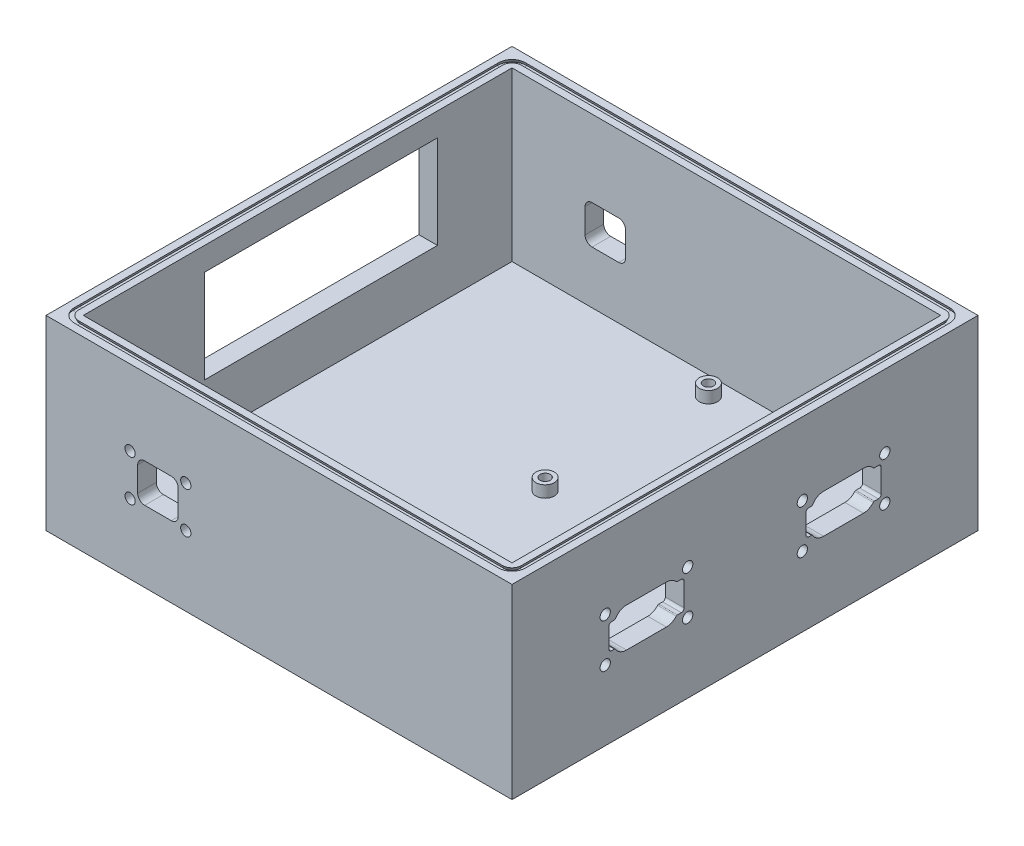
SolidWorks part; units mm, degrees
ref_plane "Front Plane" through (0, 0, 0) normal (0, 0, 1) x (1, 0, 0)
ref_plane "Top Plane" through (0, 0, 0) normal (0, 1, 0) x (1, 0, 0)
ref_plane "Right Plane" through (0, 0, 0) normal (1, 0, 0) x (0, 0, -1)
sketch "Sketch1" plane through (0, 0, 0) normal (0, 1, 0) x (1, 0, 0)
  line L1 (0, 0) -> (254, 0)
  line L2 (0, 0) -> (0, 254)
  line L3 (0, 254) -> (254, 254)
  line L4 (254, 0) -> (254, 254)
  dimension "D1" = 254
  dimension "D2" = 254
extrude "Boss-Extrude1" add sketch "Sketch1" along normal blind 101.6
sketch "12 pin hole" [suppressed] plane through (254, 0, 0) normal (1, 0, 0) x (0, 0, -1)
  line L8 (50.8, 10.16) -> (95.758, 10.16) construction
  line L9 (50.8, 10.16) -> (50.8, 34.036) construction
  line L10 (50.8, 34.036) -> (95.758, 34.036) construction
  line L11 (95.758, 10.16) -> (95.758, 34.036) construction
  line L12 (55.7357, 28.956) -> (54.2925, 28.956)
  line L13 (52.7685, 27.432) -> (52.7685, 16.764)
  line L14 (54.2925, 15.24) -> (55.7357, 15.24)
  line L16 (90.087, 29.972) -> (92.2655, 29.972)
  line L17 (93.7895, 28.448) -> (93.7895, 15.748)
  line L18 (92.2655, 14.224) -> (90.087, 14.224)
  line L21 (62.4205, 25.654) -> (84.1375, 25.654) construction
  line L22 (62.4205, 25.654) -> (62.4205, 18.542) construction
  line L23 (62.4205, 18.542) -> (84.1375, 18.542) construction
  line L24 (84.1375, 25.654) -> (84.1375, 18.542) construction
  line L25 (62.4205, 32.7152) -> (84.1375, 32.7152)
  line L26 (62.4205, 11.4808) -> (84.1375, 11.4808)
  line L27 (52.7685, 22.098) -> (50.8, 22.098) construction
  line L28 (93.7895, 22.098) -> (95.758, 22.098) construction
  arc A4 (62.4205, 32.7152) -> (56.3868, 29.3222) centre (62.4205, 25.654) ccw
  arc A5 (89.5075, 30.2392) -> (84.1375, 32.7152) centre (84.1375, 25.654) ccw
  arc A6 (62.4205, 11.4808) -> (56.3868, 14.8738) centre (62.4205, 18.542) cw
  arc A7 (89.5075, 13.9568) -> (84.1375, 11.4808) centre (84.1375, 18.542) cw
  arc A8 (90.087, 29.972) -> (89.5075, 30.2392) centre (90.087, 30.734) cw
  arc A9 (90.087, 14.224) -> (89.5075, 13.9568) centre (90.087, 13.462) ccw
  arc A10 (55.7357, 15.24) -> (56.3868, 14.8738) centre (55.7357, 14.478) cw
  arc A11 (55.7357, 28.956) -> (56.3868, 29.3222) centre (55.7357, 29.718) ccw
  arc A12 (92.2655, 29.972) -> (93.7895, 28.448) centre (92.2655, 28.448) cw
  arc A13 (93.7895, 15.748) -> (92.2655, 14.224) centre (92.2655, 15.748) cw
  arc A14 (52.7685, 16.764) -> (54.2925, 15.24) centre (54.2925, 16.764) ccw
  arc A15 (54.2925, 28.956) -> (52.7685, 27.432) centre (54.2925, 27.432) ccw
  point P25 (50.8, 22.098)
  point P28 (52.7685, 22.098)
  point P29 (93.7895, 22.098)
  point P34 (62.4205, 22.098)
  point P35 (84.1375, 22.098)
  point P44 (73.279, 10.16)
  point P46 (73.279, 11.4808)
  point P59 (93.7895, 29.972)
  point P62 (93.7895, 14.224)
  point P65 (52.7685, 15.24)
  point P68 (52.7685, 28.956)
  dimension "D4" = 41.021
  dimension "D5" = 15.748
  dimension "D11" = 7.0612
  dimension "D12" = 0.762
  dimension "D13" = 1.524
  dimension "D1" = 44.958
  dimension "D2" = 23.876
  dimension "D8" = 13.716
  dimension "D9" = 21.2344
  dimension "D10" = 21.717
sketch "Sketch2" plane through (0, 101.6, 0) normal (0, 1, 0) x (1, 0, 0)
  line L0 (0, 254) -> (0, 0) construction
  line L1 (10.16, 10.16) -> (243.84, 10.16)
  line L2 (10.16, 10.16) -> (10.16, 243.84)
  line L3 (10.16, 243.84) -> (243.84, 243.84)
  line L4 (243.84, 10.16) -> (243.84, 243.84)
  line L5 (254, 254) -> (0, 254) construction
  line L6 (254, 0) -> (254, 254) construction
  line L7 (0, 0) -> (254, 0) construction
  dimension "D1" = 10.16
  dimension "D2" = 10.16
  dimension "D3" = 10.16
  dimension "D4" = 10.16
extrude "Cut-Extrude1" cut sketch "Sketch2" against normal blind 91.44
ref_plane "Plane1" through (0, 101.6, 0) normal (0, 1, 0) x (1, 0, 0)
sketch "Sketch3" plane through (0, 101.6, 0) normal (0, 1, 0) x (1, 0, 0)
  line L4 (6.35, 11.43) -> (6.35, 242.57)
  line L5 (243.84, 243.84) -> (10.16, 243.84) construction
  line L6 (10.16, 243.84) -> (10.16, 10.16) construction
  line L7 (243.84, 10.16) -> (243.84, 243.84) construction
  line L8 (10.16, 10.16) -> (243.84, 10.16) construction
  line L13 (11.43, 247.65) -> (242.57, 247.65)
  line L14 (247.65, 242.57) -> (247.65, 11.43)
  line L15 (242.57, 6.35) -> (11.43, 6.35)
  arc A0 (6.35, 242.57) -> (11.43, 247.65) centre (11.43, 242.57) cw
  arc A1 (242.57, 247.65) -> (247.65, 242.57) centre (242.57, 242.57) cw
  arc A2 (247.65, 11.43) -> (242.57, 6.35) centre (242.57, 11.43) cw
  arc A3 (11.43, 6.35) -> (6.35, 11.43) centre (11.43, 11.43) cw
  dimension "D5" = 5.08
  dimension "D1" = 3.81
  dimension "D2" = 3.81
  dimension "D3" = 3.81
  dimension "D4" = 3.81
ref_plane "Plane2" through (0, 0, 0) normal (0, 0, 1) x (1, 0, 0)
ref_plane "Plane3" through (0, 0, -15.24) normal (0, 0, 1) x (1, 0, 0)
sketch "Sketch4" plane through (0, 0, -15.24) normal (0, 0, 1) x (1, 0, 0)
  line L0 (4.064, 101.6) -> (3.2724, 99.822)
  line L1 (6.35, 101.6) -> (7.1416, 99.822)
  line L2 (3.2724, 99.822) -> (7.1416, 99.822)
  line L5 (4.064, 101.6) -> (6.35, 101.6)
  dimension "D1" = 1.778
  dimension "D2" = 2.286
  dimension "D3" = 66
  dimension "D4" = 66
sweep "Cut-Sweep2" cut profiles "Sketch4" path "Sketch3"
sketch "Sketch13" plane through (254, 0, 0) normal (1, 0, 0) x (0, 0, -1)
  line L0 (50.8, 38.1) -> (50.8, 0) construction
  line L1 (0, 0) -> (254, 0) construction
  line L2 (50.8, 38.1) -> (0, 38.1) construction
  line L3 (0, 101.6) -> (0, 0) construction
  line L4 (203.2, 0) -> (203.2, 38.1) construction
  line L5 (203.2, 38.1) -> (254, 38.1) construction
  line L6 (254, 101.6) -> (254, 0) construction
  line B0 (50.8, 38.1) -> (95.758, 38.1) construction
  line B1 (50.8, 38.1) -> (50.8, 61.976) construction
  line B2 (50.8, 61.976) -> (95.758, 61.976) construction
  line B3 (95.758, 38.1) -> (95.758, 61.976) construction
  line B4 (55.7357, 56.896) -> (54.2925, 56.896)
  line B5 (52.7685, 55.372) -> (52.7685, 44.704)
  line B6 (54.2925, 43.18) -> (55.7357, 43.18)
  line B7 (90.087, 57.912) -> (92.2655, 57.912)
  line B8 (93.7895, 56.388) -> (93.7895, 43.688)
  line B9 (92.2655, 42.164) -> (90.087, 42.164)
  line B10 (62.4205, 60.6552) -> (84.1375, 60.6552)
  line B11 (62.4205, 39.4208) -> (84.1375, 39.4208)
  arc B12 (62.4205, 60.6552) -> (56.3868, 57.2622) centre (62.4205, 53.594) ccw
  arc B13 (89.5075, 58.1792) -> (84.1375, 60.6552) centre (84.1375, 53.594) ccw
  arc B14 (62.4205, 39.4208) -> (56.3868, 42.8138) centre (62.4205, 46.482) cw
  arc B15 (89.5075, 41.8968) -> (84.1375, 39.4208) centre (84.1375, 46.482) cw
  arc B16 (90.087, 57.912) -> (89.5075, 58.1792) centre (90.087, 58.674) cw
  arc B17 (90.087, 42.164) -> (89.5075, 41.8968) centre (90.087, 41.402) ccw
  arc B18 (55.7357, 43.18) -> (56.3868, 42.8138) centre (55.7357, 42.418) cw
  arc B19 (55.7357, 56.896) -> (56.3868, 57.2622) centre (55.7357, 57.658) ccw
  arc B20 (92.2655, 57.912) -> (93.7895, 56.388) centre (92.2655, 56.388) cw
  arc B21 (93.7895, 43.688) -> (92.2655, 42.164) centre (92.2655, 43.688) cw
  arc B22 (52.7685, 44.704) -> (54.2925, 43.18) centre (54.2925, 44.704) ccw
  arc B23 (54.2925, 56.896) -> (52.7685, 55.372) centre (54.2925, 55.372) ccw
  line B24 (158.242, 38.1) -> (203.2, 38.1) construction
  line B25 (158.242, 38.1) -> (158.242, 61.976) construction
  line B26 (158.242, 61.976) -> (203.2, 61.976) construction
  line B27 (203.2, 38.1) -> (203.2, 61.976) construction
  line B28 (163.1777, 56.896) -> (161.7345, 56.896)
  line B29 (160.2105, 55.372) -> (160.2105, 44.704)
  line B30 (161.7345, 43.18) -> (163.1777, 43.18)
  line B31 (197.529, 57.912) -> (199.7075, 57.912)
  line B32 (201.2315, 56.388) -> (201.2315, 43.688)
  line B33 (199.7075, 42.164) -> (197.529, 42.164)
  line B34 (169.8625, 60.6552) -> (191.5795, 60.6552)
  line B35 (169.8625, 39.4208) -> (191.5795, 39.4208)
  arc B36 (169.8625, 60.6552) -> (163.8288, 57.2622) centre (169.8625, 53.594) ccw
  arc B37 (196.9495, 58.1792) -> (191.5795, 60.6552) centre (191.5795, 53.594) ccw
  arc B38 (169.8625, 39.4208) -> (163.8288, 42.8138) centre (169.8625, 46.482) cw
  arc B39 (196.9495, 41.8968) -> (191.5795, 39.4208) centre (191.5795, 46.482) cw
  arc B40 (197.529, 57.912) -> (196.9495, 58.1792) centre (197.529, 58.674) cw
  arc B41 (197.529, 42.164) -> (196.9495, 41.8968) centre (197.529, 41.402) ccw
  arc B42 (163.1777, 43.18) -> (163.8288, 42.8138) centre (163.1777, 42.418) cw
  arc B43 (163.1777, 56.896) -> (163.8288, 57.2622) centre (163.1777, 57.658) ccw
  arc B44 (199.7075, 57.912) -> (201.2315, 56.388) centre (199.7075, 56.388) cw
  arc B45 (201.2315, 43.688) -> (199.7075, 42.164) centre (199.7075, 43.688) cw
  arc B46 (160.2105, 44.704) -> (161.7345, 43.18) centre (161.7345, 44.704) ccw
  arc B47 (161.7345, 56.896) -> (160.2105, 55.372) centre (161.7345, 55.372) ccw
  dimension "D1" = 50.8
  dimension "D2" = 38.1
sketch_block_instance "Block7-3"
sketch_block "Block7" parameters "D6"=7.0612, "D7"=0.762, "D8"=1.524, "D1"=44.958, "D2"=23.876, "D3"=41.021, "D4"=21.2344, "D5"=21.717
sketch_block_instance "Block7-4"
extrude "Cut-Extrude10" cut sketch "Sketch13" against normal up to next
sketch "12 pin mount" plane through (254, 0, 0) normal (1, 0, 0) x (0, 0, -1)
  circle A0 centre (95.758, 61.976) radius 2.8
  circle A1 centre (95.758, 38.1) radius 2.8
  circle A2 centre (50.8, 38.1) radius 2.8
  circle A3 centre (50.8, 61.976) radius 2.8
  circle A4 centre (158.242, 61.976) radius 2.8
  circle A5 centre (203.2, 61.976) radius 2.8
  circle A6 centre (203.2, 38.1) radius 2.8
  circle A7 centre (158.242, 38.1) radius 2.8
  dimension "D1" = 5.6
extrude "Cut-Extrude3" cut sketch "12 pin mount" against normal blind 5.5
sketch "4 pin connector" plane through (0, 0, 0) normal (0, 0, 1) x (1, 0, 0)
  line L0 (76.2, 0) -> (76.2, 38.1) construction
  line L1 (0, 0) -> (254, 0) construction
  line L2 (76.2, 38.1) -> (254, 38.1) construction
  line L3 (254, 101.6) -> (254, 0) construction
  line L5 (45.847, 60.5536) -> (76.2, 60.5536) construction
  line L6 (45.847, 60.5536) -> (45.847, 38.1) construction
  line L7 (45.847, 38.1) -> (76.2, 38.1) construction
  line L8 (76.2, 60.5536) -> (76.2, 38.1) construction
  line L9 (53.7845, 59.817) -> (68.2625, 59.817)
  line L10 (49.9745, 56.007) -> (49.9745, 42.6466)
  line L11 (53.7845, 38.8366) -> (68.2625, 38.8366)
  line L12 (72.0725, 56.007) -> (72.0725, 42.6466)
  line L13 (61.0235, 38.8366) -> (61.0235, 59.817) construction
  line L14 (49.9745, 49.3268) -> (72.0725, 49.3268) construction
  arc A0 (68.2625, 59.817) -> (72.0725, 56.007) centre (68.2625, 56.007) cw
  arc A1 (68.2625, 38.8366) -> (72.0725, 42.6466) centre (68.2625, 42.6466) ccw
  arc A2 (49.9745, 42.6466) -> (53.7845, 38.8366) centre (53.7845, 42.6466) ccw
  arc A3 (53.7845, 59.817) -> (49.9745, 56.007) centre (53.7845, 56.007) ccw
  point P4 (61.0235, 49.3268)
  point P12 (61.0235, 38.1)
  point P15 (76.2, 49.3268)
  point P20 (72.0725, 59.817)
  point P24 (72.0725, 38.8366)
  point P29 (49.9745, 59.817)
  dimension "D1" = 22.098
  dimension "D7" = 3.81
  dimension "D2" = 22.4536
  dimension "D3" = 30.353
  dimension "D4" = 38.1
  dimension "D5" = 177.8
  dimension "D6" = 20.9804
extrude "Cut-Extrude5" cut sketch "4 pin connector" against normal up to next
extrude "Cut-Extrude6" cut sketch "Sketch5<2>" along normal up to next from surface starting at face at (127, 50.8, -254)
sketch "Sketch5<2>" plane through (0, 0, 0) normal (0, 0, 1) x (1, 0, 0) same geometry as "4 pin connector"
sketch "Sketch6" plane through (0, 0, 0) normal (0, 0, 1) x (1, 0, 0)
  circle A0 centre (76.2, 60.5536) radius 2.8
  circle A1 centre (76.2, 38.1) radius 2.8
  circle A2 centre (45.847, 38.1) radius 2.8
  circle A3 centre (45.847, 60.5536) radius 2.8
  dimension "D1" = 5.6
extrude "Cut-Extrude7" cut sketch "Sketch6" against normal blind 5.5
extrude "Cut-Extrude8" cut sketch "Sketch6<2>" along normal blind 5.5 from surface starting at face at (61.0235, 49.3268, -254)
sketch "Sketch6<2>" plane through (0, 0, 0) normal (0, 0, 1) x (1, 0, 0) same geometry as "Sketch6"
sketch "Sketch7" plane through (0, 10.16, 0) normal (0, 1, 0) x (1, 0, 0)
  line L0 (193.04, 189.1889) -> (243.84, 189.1889) construction
  line L1 (243.84, 10.16) -> (243.84, 243.84) construction
  line L5 (193.04, 144.6739) -> (127.38, 144.6739) construction
  line L6 (193.04, 144.6739) -> (193.04, 233.7039) construction
  line L7 (193.04, 233.7039) -> (127.38, 233.7039) construction
  line L8 (127.38, 144.6739) -> (127.38, 233.7039) construction
  circle A0 centre (127.38, 144.6739) radius 5
  circle A1 centre (193.04, 144.6739) radius 5
  circle A2 centre (193.04, 233.7039) radius 5
  circle A3 centre (127.38, 233.7039) radius 5
  dimension "D1" = 10
  dimension "D2" = 89.03
  dimension "D3" = 65.66
  dimension "D4" = 50.8
sketch "Sketch8" plane through (0, 10.16, 0) normal (0, 1, 0) x (1, 0, 0)
  circle A0 centre (127.38, 233.7039) radius 2.8
  circle A1 centre (193.04, 233.7039) radius 2.8
  circle A2 centre (193.04, 144.6739) radius 2.8
  circle A3 centre (127.38, 144.6739) radius 2.8
  dimension "D1" = 5.6
extrude "Boss-Extrude2" add sketch "Sketch7" along normal blind 6.35
extrude "Cut-Extrude9" cut sketch "Sketch8" against normal blind 5.5 from surface starting at face at (193.04, 16.51, -139.6739)
sketch "Sketch14" plane through (0, 0, 0) normal (-1, 0, 0) x (0, 0, 1)
  line L0 (-254, 101.6) -> (-254, 0) construction
  line L1 (-203.2, 88.9) -> (-76.2, 88.9)
  line L2 (-203.2, 88.9) -> (-203.2, 38.1)
  line L3 (-203.2, 38.1) -> (-76.2, 38.1)
  line L4 (-76.2, 88.9) -> (-76.2, 38.1)
  line L5 (-254, 0) -> (0, 0) construction
  point P6 (-76.2, 63.5)
  dimension "D1" = 177.8
  dimension "D2" = 50.8
  dimension "D3" = 50.8
  dimension "D4" = 38.1
extrude "Cut-Extrude11" cut sketch "Sketch14" against normal up to next
equation "\"M4 insert  width\"= 5.6mm"
equation "\"M4 insert  depth\"= 5.5mm"
equation "\"depth\"=0.1"
